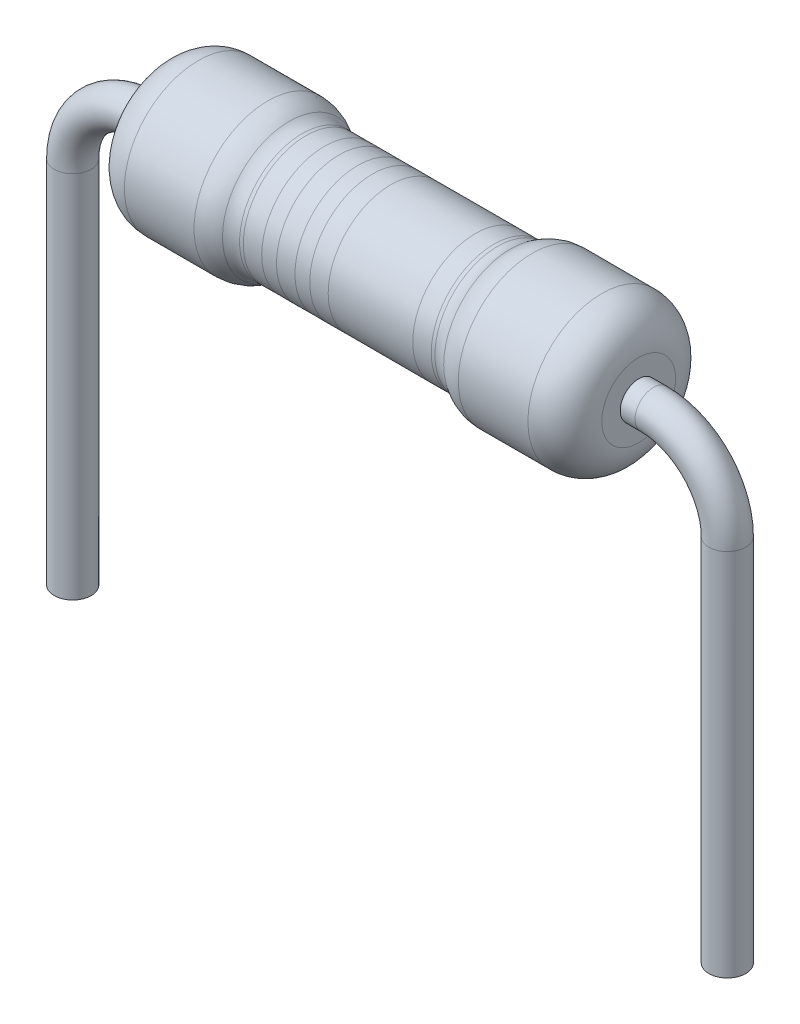
SolidWorks part; units mm, degrees
material "Silicon Dioxide"
ref_plane "Front Plane" through (0, 0, 0) normal (0, 0, 1) x (1, 0, 0)
ref_plane "Top Plane" through (0, 0, 0) normal (0, 1, 0) x (1, 0, 0)
ref_plane "Right Plane" through (0, 0, 0) normal (1, 0, 0) x (0, 0, -1)
sketch "Sketch58" plane through (0, 0, 0) normal (1, 0, 0) x (0, 0, -1)
  circle A0 centre (0, 0) radius 1
  dimension "D1" = 2
extrude "Boss-Extrude1" add sketch "Sketch58" along normal blind 6.464
sketch "Sketch59" plane through (0, 0, 0) normal (0, 0, 1) x (1, 0, 0)
  line L0 (0, 1) -> (0, -1) construction
  line L1 (1.8, 1.15) -> (4.664, 1.15)
  line L2 (1.8, 1.15) -> (1.8, 0.85)
  line L3 (1.8, 0.85) -> (4.664, 0.85)
  line L4 (4.664, 1.15) -> (4.664, 0.85)
  line L5 (6.464, -1) -> (6.464, 1) construction
  line L7 (4.664, 1) -> (7.3855, 1) construction
  line L8 (6.464, 1) -> (0, 1) construction
  dimension "D1" = 1.8
  dimension "D2" = 1.8
  dimension "D3" = 0.3
revolve "Cut-Revolve1" cut sketch "Sketch59" angle 360 about axis through (6.464, 0, 0) along (-1, 0, 0)
fillet "Fillet6" radius 0.5 4 edges at (4.664, 0, -1) (1.8, 0, 1) (6.464, 0, -1) (0, 0, -1)
fillet "Fillet7" radius 0.3 2 edges at (4.664, 0, -0.85) (1.8, 0, -0.85)
sketch "Sketch54" plane through (0, 0, 0) normal (1, 0, 0) x (0, 0, -1)
  circle A0 centre (0, 0) radius 0.25
  dimension "D1" = 0.5
sketch "Sketch55" plane through (0, 0, 0) normal (0, 0, 1) x (1, 0, 0)
  line L0 (0, 0) -> (-0.2, 0)
  line L1 (-1.2, -1) -> (-1.2, -6)
  arc A0 (-0.2, 0) -> (-1.2, -1) centre (-0.2, -1) ccw
  dimension "D2" = 5
ref_plane "Plane1" through (3.232, 0, 0) normal (1, 0, 0) x (0, 0, -1)
ref_plane "Plane2" through (0, -6, 0) normal (0, 1, 0) x (1, 0, 0)
sketch "Sketch60" plane through (0, -6, 0) normal (0, 1, 0) x (1, 0, 0)
  line L1 (1.9593, 4) -> (2.2093, 4)
  line L2 (1.9593, 4) -> (1.9593, -4)
  line L3 (1.9593, -4) -> (2.2093, -4)
  line L4 (2.2093, 4) -> (2.2093, -4)
  line L5 (1.9593, 0) -> (2.6746, 0) construction
  line L6 (2.4093, 4) -> (2.6593, 4)
  line L7 (2.4093, 4) -> (2.4093, -4)
  line L8 (2.4093, -4) -> (2.6593, -4)
  line L9 (2.6593, 4) -> (2.6593, -4)
  line L10 (2.4093, 0) -> (3.2519, 0) construction
  line L11 (2.8593, 4) -> (3.1093, 4)
  line L12 (2.8593, 4) -> (2.8593, -4)
  line L13 (2.8593, -4) -> (3.1093, -4)
  line L14 (3.1093, 4) -> (3.1093, -4)
  line L15 (2.8593, 0) -> (3.9566, 0) construction
  line L16 (4.2547, 4) -> (4.5047, 4)
  line L17 (4.2547, 4) -> (4.2547, -4)
  line L18 (4.2547, -4) -> (4.5047, -4)
  line L19 (4.5047, 4) -> (4.5047, -4)
  line L20 (4.2547, 0) -> (5.2023, 0) construction
  line L24 (1.9093, 0.85) -> (1.9093, -0.85) construction
  line L25 (4.5547, 0.85) -> (4.5547, -0.85) construction
  dimension "D3" = 8
  dimension "D4" = 0.2
  dimension "D5" = 0.2
  dimension "D6" = 0.25
  dimension "D7" = 0.25
  dimension "D8" = 8
  dimension "D9" = 8
  dimension "D10" = 0.25
  dimension "D12" = 8
  dimension "D2" = 0.05
  dimension "D11" = 0.05
split line "Split Line1"
sweep "Sweep1" add profiles "Sketch54" path "Sketch55"
mirror "Mirror1" about plane through (3.232, 0, 0) normal (1, 0, 0) of "Sweep1"
equation "\"ResistorBody\"= \"TotalLeadDistance\" - ( ( 1 + \"LeadLength\" ) * 2 )'How long is the body of the resistor?"
equation "\"ResistorDiameter\"= 2.0'Whats the diameter of the resistor body?"
equation "\"LeadDiameter\"= 0.5'Whats the diameter of the leads?"
equation "\"LeadLength\"= .2'How long are the leads that exit the body before bending down?"
equation "\"LeadLengthPCB\"= 5'How long do the leads need to be for mounting into the PCB"
equation "\"D1@Sketch54\"=\"LeadDiameter\""
equation "\"D1@Sketch55\"=\"LeadLength\""
equation "\"D2@Sketch55\"=\"LeadLengthPCB\""
equation "\"D1@Sketch58\"=\"ResistorDiameter\""
equation "\"D1@Boss-Extrude1\"=\"ResistorBody\""
equation "\"BandWidth\"= .25'How wide are the color bands?"
equation "\"D1@Sketch60\"=\"BandWidth\""
equation "\"D6@Sketch60\"=\"BandWidth\""
equation "\"D7@Sketch60\"=\"BandWidth\""
equation "\"D10@Sketch60\"=\"BandWidth\""
equation "\"BandSeparation\"= .2'How much separation between band colors?"
equation "\"D4@Sketch60\"=\"BandSeparation\""
equation "\"D5@Sketch60\"=\"BandSeparation\""
equation "\"TotalLeadDistance\"= 8.864'Enter the desired distance for the PCB hole mounting"
